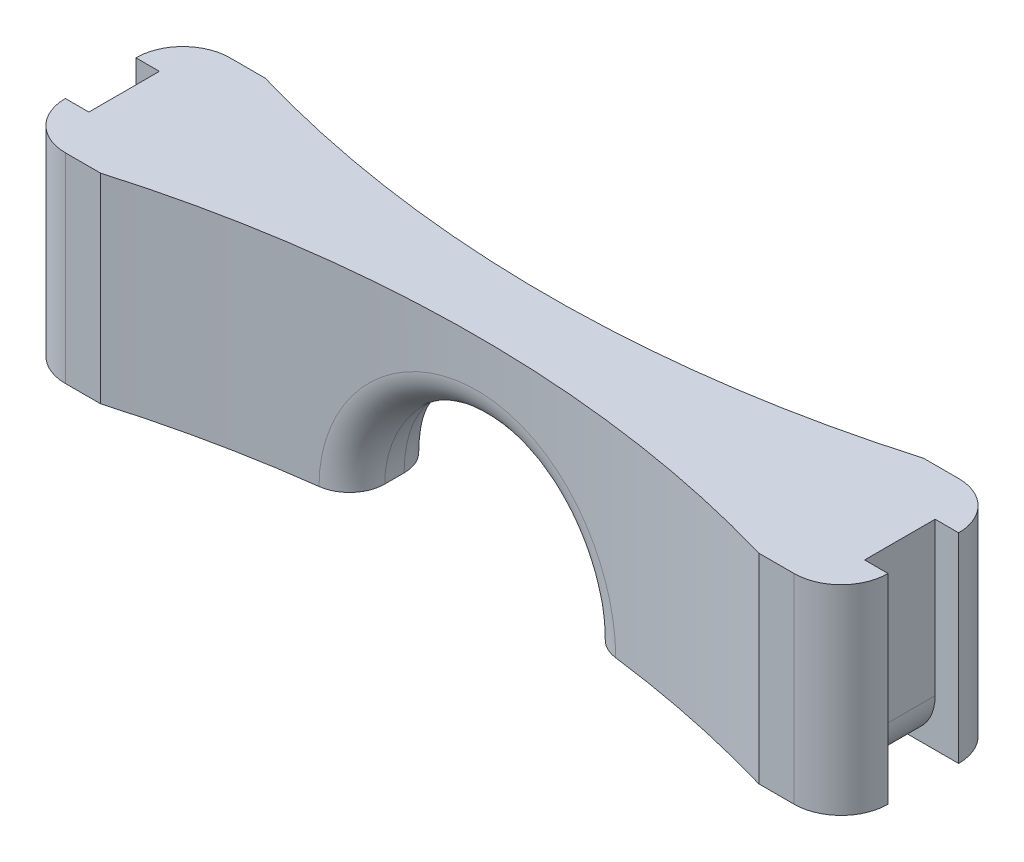
SolidWorks part; units mm, degrees
ref_plane "Front Plane" through (0, 0, 0) normal (0, 0, 1) x (1, 0, 0)
ref_plane "Top Plane" through (0, 0, 0) normal (0, 1, 0) x (1, 0, 0)
ref_plane "Right Plane" through (0, 0, 0) normal (1, 0, 0) x (0, 0, -1)
sketch "Sketch1" plane through (0, 0, 0) normal (0, 0, 1) x (1, 0, 0)
  line L0 (55, 0) -> (-55, 0) construction
  line L1 (0, 0) -> (12.5, 0)
  line L2 (0, 0) -> (0, 8.5)
  line L3 (0, 8.5) -> (35, 8.5)
  line L4 (35, 0) -> (35, 8.5)
  line L5 (22.5, 0) -> (35, 0)
  arc A0 (22.5, 0) -> (12.5, 0) centre (17.5, 0) ccw
  dimension "D3" = 10
  dimension "D1" = 8.5
  dimension "D2" = 35
  dimension "D4" = 17.5
extrude "Boss-Extrude1" add sketch "Sketch1" along normal blind 7
sketch "Sketch2" plane through (0, 8.5, 0) normal (0, 1, 0) x (1, 0, 0)
  line L0 (-4.675, 0) -> (4.675, 0) construction
  line L1 (40.4419, -2) -> (34, -2)
  line L2 (40.4419, -2) -> (40.4419, -5)
  line L3 (40.4419, -5) -> (34, -5)
  line L4 (34, -2) -> (34, -5)
  line L5 (-4.2669, -2) -> (1, -2)
  line L6 (-4.2669, -2) -> (-4.2669, -5)
  line L7 (-4.2669, -5) -> (1, -5)
  line L8 (1, -2) -> (1, -5)
  line L9 (0, -3.85) -> (0, 3.85) construction
  line L10 (35, -7) -> (35, 0) construction
  line L11 (17.5, 48) -> (17.5, -7) construction
  line L12 (35, -7) -> (0, -7) construction
  line L13 (35, -3.5) -> (28.47, -3.5) construction
  circle A0 centre (17.5, 48) radius 50
  circle A1 centre (17.5, -55) radius 50
  dimension "D5" = 100
  dimension "D6" = 2
  dimension "D1" = 3
  dimension "D2" = 2
  dimension "D3" = 1
  dimension "D4" = 1
extrude "Cut-Extrude1" cut sketch "Sketch2" against normal through all
fillet "Fillet1" radius 2 6 edges at (35, 4.25, 0) (35, 4.25, 7) (0, 4.25, 7) (0, 4.25, 0) (1, 0, 3.5) (34, 0, 3.5)
fillet "Fillet2" radius 1.5 2 edges at (18.0669, 4.9678, 1.9968) (16.9331, 4.9678, 5.0032)
